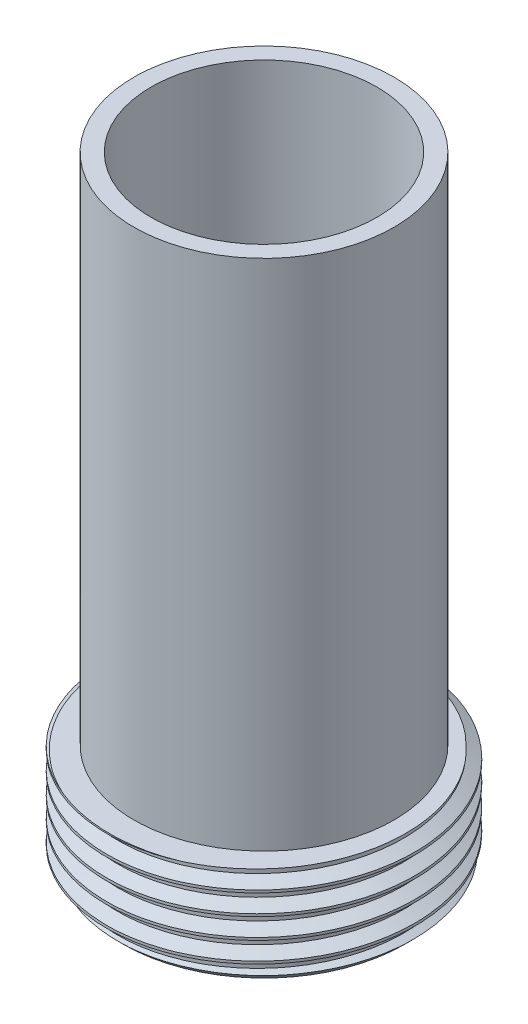
SolidWorks part; units mm, degrees
ref_plane "Front Plane" through (0, 0, 0) normal (0, 0, 1) x (1, 0, 0)
ref_plane "Top Plane" through (0, 0, 0) normal (0, 1, 0) x (1, 0, 0)
ref_plane "Right Plane" through (0, 0, 0) normal (1, 0, 0) x (0, 0, -1)
sketch "Sketch2" plane through (0, 0, 0) normal (0, 1, 0) x (1, 0, 0)
  circle A0 centre (0, 0) radius 16.5
  circle A1 centre (0, 0) radius 19
  dimension "D1" = 33
  dimension "D2" = 38
extrude "Boss-Extrude1" add sketch "Sketch2" along normal blind 42
sketch "Sketch3" plane through (0, 0, 0) normal (0, -1, 0) x (1, 0, 0)
  circle A0 centre (0, 0) radius 22.5
  circle A1 centre (0, 0) radius 16.5
  circle A2 centre (0, 0) radius 16.5 construction
  dimension "D1" = 45
extrude "Boss-Extrude2" add sketch "Sketch3" against normal blind 15
thread "Thread1" [suppressed] pitch 4.5 start angle 0, offset 11, length 0, pitch 4, diameter 45
ref_plane "Plane1" through (22.5, -11, 0) normal (0, 0, 1) x (1, 0, 0)
sketch "Thread Profile1" plane through (22.5, -11, 0) normal (0, 0, 1) x (1, 0, 0)
  line L0 (0, 0) -> (0, 4.5) construction
  line L11 (0, 0) -> (0, 3.9375)
  line L12 (0, 3.9375) -> (-2.4357, 2.5312)
  line L13 (-2.4357, 2.5312) -> (-2.4357, 1.4062)
  line L15 (-2.4357, 1.4062) -> (0, 0)
  line L17 (-2.4357, 1.9687) -> (0, 1.9687) construction
  point P2 (0, 0)
  dimension "Pitch" = 4.5
  dimension "Profile_Angle" = 60
  dimension "Profile_Land" = 1.125
  dimension "Profile_Height" = 2.4357
sketch "Sketch4" plane through (0, 42, 0) normal (0, 1, 0) x (1, 0, 0)
  circle A0 centre (0, 0) radius 16.5
  circle A1 centre (0, 0) radius 19
  circle A2 centre (0, 0) radius 19
  circle A3 centre (0, 0) radius 16.5 construction
  dimension "D1" = 0
extrude "Boss-Extrude4" add sketch "Sketch4" along normal blind 48
sketch "Sketch5" plane through (0, 0, 0) normal (0, -1, 0) x (1, 0, 0)
  circle A0 centre (0, 0) radius 22.5
  dimension "D1" = 45
curve "Helix/Spiral1" pitch 3 height 15 radius 22.5 centre (0, 0, 0) axis (0, 1, 0) start towards (0, 0, -1)
sketch "Sketch18" plane through (0, 0, 0) normal (1, 0, 0) x (0, 0, -1)
  line L0 (22.5, -1.3125) -> (22.5, 1.3125)
  line L5 (22.5, 1.3125) -> (20.8762, 0.375)
  line L6 (20.8762, 0.375) -> (20.8762, -0.375)
  line L7 (20.8762, -0.375) -> (22.5, -1.3125)
  line L8 (22.5, 0) -> (20.8762, 0) construction
  line L9 (-16.5, 0) -> (16.5, 0) construction
  point P5 (0, 0)
  point P7 (0, 0)
  point P8 (22.5, -2.59)
  dimension "D1" = 1.6237
  dimension "D2" = 22.5
  dimension "D3" = 60
  dimension "D4" = 0.75
sweep "Cut-Sweep7" cut profiles "Sketch18" path "Helix/Spiral1" align with end faces yes
sketch "Sketch19" plane through (0, 0, 0) normal (0, 0, 1) x (1, 0, 0)
  line L0 (22.5, 2) -> (22.5, 0)
  line L1 (22.5, 0) -> (20.5, 0)
  line L2 (20.5, 0) -> (22.5, 2)
  line L4 (22.5, 0.5625) -> (22.5, 0.9375) construction
  line L5 (8.5864, 0) -> (21.5422, 0) construction
  line L6 (0, 0) -> (0, 23.7592) construction
  dimension "D1" = 2
revolve "Cut-Revolve1" cut sketch "Sketch19" angle 360 about L6
